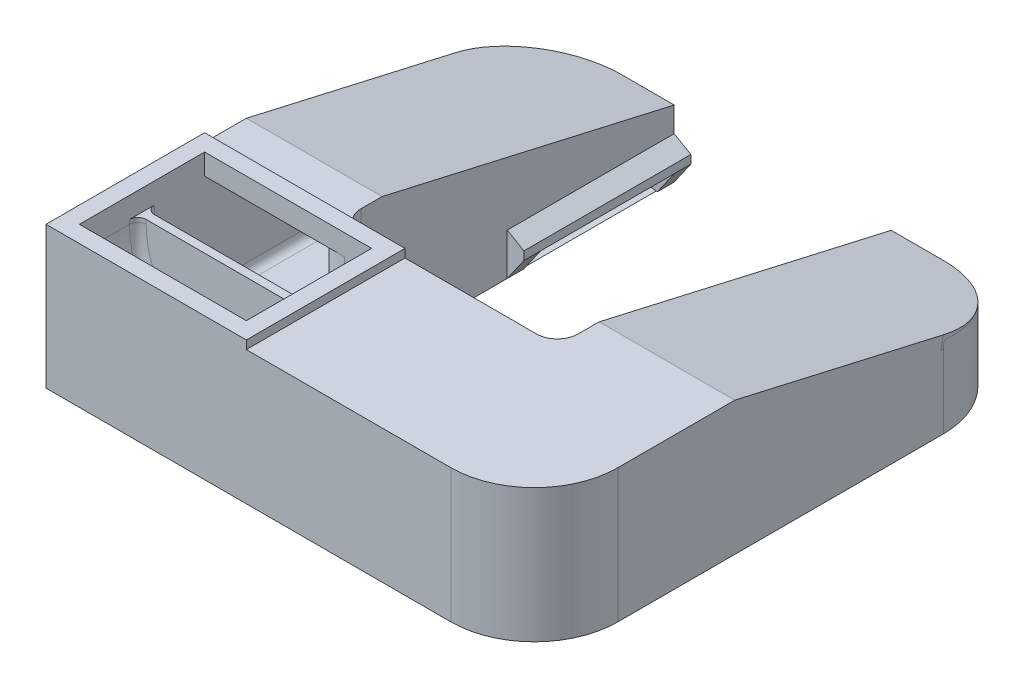
SolidWorks part; units mm, degrees
ref_plane "Front Plane" through (0, 0, 0) normal (0, 0, 1) x (1, 0, 0)
ref_plane "Top Plane" through (0, 0, 0) normal (0, 1, 0) x (1, 0, 0)
ref_plane "Right Plane" through (0, 0, 0) normal (1, 0, 0) x (0, 0, -1)
sketch "Sketch1" plane through (0, 0, 0) normal (0, 1, 0) x (1, 0, 0)
  line L0 (-13, 40) -> (-13, 0)
  line L1 (-13, 0) -> (13, 0)
  line L2 (13, 0) -> (13, 40)
  line L3 (13, 40) -> (19.25, 40)
  line L4 (29.25, 30) -> (29.25, -9)
  line L5 (19.25, -19) -> (-29.25, -19)
  line L6 (-29.25, -19) -> (-29.25, 30)
  line L7 (-19.25, 40) -> (-13, 40)
  arc A0 (19.25, 40) -> (29.25, 30) centre (19.25, 30) cw
  arc A1 (-29.25, 30) -> (-19.25, 40) centre (-19.25, 30) cw
  arc A2 (29.25, -9) -> (19.25, -19) centre (19.25, -9) cw
  point P11 (29.25, 40)
  point P14 (-29.25, 40)
  dimension "D7" = 10
  dimension "D8" = 10
  dimension "D1" = 26
  dimension "D2" = 13
  dimension "D3" = 40
  dimension "D4" = 16.25
  dimension "D5" = 16.25
  dimension "D6" = 19
extrude "Boss-Extrude1" add sketch "Sketch1" along normal blind 2
sketch "Sketch2" plane through (0, 2, 0) normal (0, 1, 0) x (1, 0, 0)
  line L0 (-29.25, 30) -> (-29.25, -19)
  line L1 (-29.25, -19) -> (19.25, -19)
  line L2 (-19.25, 40) -> (-13, 40)
  line L3 (-13, 40) -> (-13, 0)
  line L4 (-13, 0) -> (13, 0)
  line L5 (13, 0) -> (13, 40)
  line L6 (13, 40) -> (19.25, 40)
  line L7 (29.25, 30) -> (29.25, -9)
  line L8 (27.25, 30) -> (27.25, -9)
  line L9 (-27.25, -17) -> (19.25, -17)
  line L10 (-27.25, 30) -> (-27.25, -17)
  line L11 (-19.25, 38) -> (-15, 38)
  line L12 (-15, 38) -> (-15, -2)
  line L13 (-15, -2) -> (15, -2)
  line L14 (15, -2) -> (15, 38)
  line L15 (15, 38) -> (19.25, 38)
  arc A0 (-19.25, 40) -> (-29.25, 30) centre (-19.25, 30) ccw
  arc A1 (19.25, -19) -> (29.25, -9) centre (19.25, -9) ccw
  arc A2 (19.25, 40) -> (29.25, 30) centre (19.25, 30) cw
  arc A3 (19.25, 38) -> (27.25, 30) centre (19.25, 30) cw
  arc A4 (19.25, -17) -> (27.25, -9) centre (19.25, -9) ccw
  arc A5 (-19.25, 38) -> (-27.25, 30) centre (-19.25, 30) ccw
  dimension "D1" = 2
extrude "Boss-Extrude2" add sketch "Sketch2" along normal blind 14
sketch "Sketch3" plane through (0, 2, 0) normal (0, 1, 0) x (1, 0, 0)
  line L0 (-27.25, 30) -> (-27.25, -17) construction
  line L1 (-27.25, -9) -> (-7.25, -9)
  line L11 (15, -2) -> (-15, -2) construction
  line L15 (-7.25, -9) -> (-7.25, -2)
  line L16 (-27.25, -10) -> (-6.25, -10)
  line L18 (-7.25, -2) -> (15, -2)
  line L19 (-27.25, -9) -> (-27.25, -10)
  line L21 (-6.25, -10) -> (7, -10)
  line L23 (-27.25, -17) -> (19.25, -17) construction
  arc A0 (15, -2) -> (7, -10) centre (7, -2) cw
  dimension "D1" = 20
  dimension "D2" = 7
  dimension "D4" = 1
  dimension "D5" = 1
extrude "Boss-Extrude3" add sketch "Sketch3" along normal up to surface (14 mm away) up to face at (1.9383, 16, -15.9156)
fillet "Fillet1" radius 7 2 edges at (-7.25, 2, 5.5) (-17.25, 2, 9)
fillet "Fillet9" radius 12 1 edges at (-27.25, 2, 13.5)
fillet "Fillet6" radius 2.5 2 edges at (13, 8, 0) (-13, 8, 0)
fillet "Fillet7" radius 4.5 1 edges at (-15, 9, 2)
fillet "Fillet8" radius 1 22 edges at (-7.25, 12.5, 2) (-8.1161, 5.6273, 2) (-12.9756, 2.117, 1.2579) (12.6569, 2, 7.6569) (15, 2, -18) (17.125, 2, -38) (24.9069, 2, -35.6569) (27.25, 2, -10.5) (24.9069, 2, 14.6569) (2, 2, 17) (-4.125, 2, 10) (-24.9069, 2, -35.6569) (-17.125, 2, -38) (-15, 2, -20.25) (-14.8084, 2, -1.201) (-27.25, 2, -14) (-27.25, 15, 17) (-23.7353, 5.5147, 17) (-27.25, 15, 10) (-23.7353, 5.5147, 10) (-27.25, 12.5, 9) (-27.25, 4.0503, 6.9497)
sketch "Sketch4" plane through (0, 16, 0) normal (0, 1, 0) x (1, 0, 0)
  line L1 (-10.5, -2) -> (-27.25, -2)
  line L2 (-7.25, -10) -> (-7.25, -17)
  line L3 (-26.25, -17) -> (19.25, -17) construction
  line L6 (-15, 2.5) -> (-15, 38)
  line L7 (-15, 38) -> (-19.25, 38)
  line L8 (-27.25, 30) -> (-27.25, -2)
  line L9 (-7.25, -17) -> (19.25, -17)
  line L10 (27.25, -9) -> (27.25, 30)
  line L11 (19.25, 38) -> (15, 38)
  line L12 (15, 38) -> (15, -2)
  line L13 (7, -10) -> (-7.25, -10)
  line L14 (-26.25, -10) -> (7, -10) construction
  line L15 (-7.25, -3) -> (-7.25, -9) construction
  arc A1 (7, -10) -> (15, -2) centre (7, -2) ccw
  arc A2 (-19.25, 38) -> (-27.25, 30) centre (-19.25, 30) ccw
  arc A3 (19.25, 38) -> (27.25, 30) centre (19.25, 30) cw
  arc A4 (19.25, -17) -> (27.25, -9) centre (19.25, -9) ccw
  arc A6 (-15, 2.5) -> (-10.5, -2) centre (-10.5, 2.5) ccw
  arc A7 (-13.5682, -0.7918) -> (-10.5, -2) centre (-10.5, 2.5) ccw construction
extrude "Boss-Extrude4" add sketch "Sketch4" against normal blind 1.5
sketch "Sketch5" plane through (0, 16, 0) normal (0, 1, 0) x (1, 0, 0)
  line L0 (19.25, -17) -> (-15.25, -17) construction
  line L1 (-27.25, -2) -> (-7.25, -2)
  line L2 (-27.25, -2) -> (-27.25, -17)
  line L3 (-27.25, -17) -> (-7.25, -17)
  line L4 (-7.25, -2) -> (-7.25, -17)
  line L5 (-7.25, -10) -> (-7.25, -17) construction
extrude "Cut-Extrude1" cut sketch "Sketch5" against normal blind 1.5
sketch "Sketch6" plane through (0, 16, 0) normal (0, 1, 0) x (1, 0, 0)
  line L0 (-29.25, -19) -> (19.25, -19) construction
  line L1 (-27.25, -17) -> (-7.25, -17)
  line L2 (-27.25, -17) -> (-27.25, -2)
  line L3 (-27.25, -2) -> (-7.25, -2)
  line L4 (-7.25, -17) -> (-7.25, -2)
  line L5 (-5.25, -19) -> (-29.25, -19)
  line L6 (-5.25, -19) -> (-5.25, 0)
  line L7 (-5.25, 0) -> (-29.25, 0)
  line L8 (-29.25, -19) -> (-29.25, 0)
  dimension "D1" = 2
  dimension "D2" = 2
  dimension "D3" = 2
extrude "Boss-Extrude5" add sketch "Sketch6" along normal blind 1
ref_plane "Plane1" through (0, 0, -30) normal (0, 0, -1) x (-1, 0, 0)
sketch "Sketch7" plane through (0, 0, -30) normal (0, 0, -1) x (-1, 0, 0)
  line L0 (-13, 2) -> (0, 0) construction
  line L1 (-13, 0) -> (-13, 16) construction
  line L2 (0, 0) -> (13, 2) construction
  line L3 (13, 16) -> (13, 0) construction
  line L4 (-19.25, 0) -> (-13, 0) construction
  line L5 (10.5, 0) -> (13, 0) construction
  line L6 (19.25, 0) -> (29.25, 0) construction
  line L7 (26.1529, 2) -> (8.6205, -0.6973)
  line L8 (8.6205, -0.6973) -> (8.0123, 3.2562)
  line L9 (8.0123, 3.2562) -> (25.5447, 5.9535)
  line L10 (25.5447, 5.9535) -> (26.1529, 2)
  dimension "D1" = 2
  dimension "D2" = 2
  dimension "D3" = 2
  dimension "D4" = 4
  dimension "D5" = 2
extrude "Cut-Extrude2" cut sketch "Sketch7" against normal blind 8
sketch "Sketch9" plane through (-13, 0, 0) normal (1, 0, 0) x (0, 0, -1)
  line L0 (5, 16) -> (40, 8)
  line L1 (2.5, 16) -> (40, 16) construction
  line L2 (40, 16) -> (40, 0) construction
  line L3 (40, 8) -> (40, 16)
  line L4 (40, 16) -> (5, 16)
  dimension "D1" = 35
extrude "Cut-Extrude3" cut sketch "Sketch9" against normal through all
sketch "Sketch10" plane through (0, 16.2917, -3.7238) normal (0, 0.9749, -0.2228) x (1, 0, 0)
  line L0 (-29.25, 26.9538) -> (-29.25, 1.3091)
  line L1 (-29.25, 1.3091) -> (-13, 1.3091)
  line L2 (-13, 1.3091) -> (-13, 37.2117)
  line L3 (-13, 1.3091) -> (-13, 37.2117) construction
  line L4 (-13, 37.2117) -> (-19.25, 37.2117)
  line L5 (-13, 37.2117) -> (-13, 38.9943) construction
  arc A1 (-19.25, 37.2117) -> (-29.25, 26.9538) centre (-19.1042, 27.0664) ccw
  ellipse E0 centre (-19.25, 26.9538) end of major axis (-19.25, 37.2117) minor radius 10 (-19.25, 37.2117) -> (-29.25, 26.9538) ccw construction
extrude "Boss-Extrude6" add sketch "Sketch10" against normal blind 1.5
sketch "Sketch11" plane through (-0.3041, -1.9767, 0) normal (0.1521, 0.9884, 0) x (0.9884, -0.1521, 0)
  line L0 (-27.3893, 30) -> (-12.8488, 30)
  line L1 (-19.3893, 38) -> (-12.8488, 38)
  line L2 (-12.8488, 30) -> (-12.8488, 38)
  line L3 (-19.4823, 38) -> (-15.2817, 38) construction
  arc A0 (-27.3893, 30) -> (-19.3893, 38) centre (-19.3893, 30) cw
extrude "Cut-Extrude4" cut sketch "Sketch11" along normal blind 4
mirror "Mirror2" about plane through (0, 0, 0) normal (1, 0, 0) of "Cut-Extrude4", "Boss-Extrude6", "Cut-Extrude3", "Cut-Extrude2"
sketch "Sketch12" plane through (0, 0, -38) normal (0, 0, 1) x (1, 0, 0)
  line L0 (-13, 4.0235) -> (-11, 2.8688)
  line L1 (-11, 2.8688) -> (-11, 3.8688)
  line L2 (-11, 3.8688) -> (-13, 5.0235)
  line L3 (-13, 5.0235) -> (-13, 4.0235)
  line L4 (-13, 0) -> (-13, 4.0235) construction
  dimension "D1" = 2
  dimension "D2" = 1
  dimension "D3" = 60
extrude "Boss-Extrude7" add sketch "Sketch12" along normal up to surface (16 mm away) up to face at (-15.8713, 2.1639, -22)
sketch "Sketch13" plane through (0, 0, -38) normal (0, 0, -1) x (-1, 0, 0)
  line L0 (11, 3.8688) -> (11, 2.8688)
  line L1 (11, 2.8688) -> (11, 3.8688) construction
  line L2 (11, 2.8688) -> (13, 0)
  line L3 (13, 0) -> (13, 5.0235)
  line L4 (13, 16) -> (13, 0) construction
  line L5 (11, 3.8688) -> (13, 5.0235) construction
  line L6 (13, 5.0235) -> (11, 3.8688)
  line L7 (13, 4.0235) -> (11, 2.8688) construction
  point P12 (0, 0)
  point P13 (11, 2.8688)
extrude "Boss-Extrude8" add sketch "Sketch13" along normal blind 2
sketch "Sketch14" plane through (0, 0, -22) normal (0, 0, 1) x (1, 0, 0)
  line L0 (-13, 5.0235) -> (-13, 0)
  line L1 (-13, 0) -> (-11, 2.8688)
  line L2 (-11, 2.8688) -> (-11, 3.8688)
  line L3 (-11, 3.8688) -> (-13, 5.0235)
extrude "Boss-Extrude9" add sketch "Sketch14" along normal blind 2
mirror "Mirror3" about plane through (0, 0, 0) normal (1, 0, 0) of "Boss-Extrude8", "Boss-Extrude9", "Boss-Extrude7"
